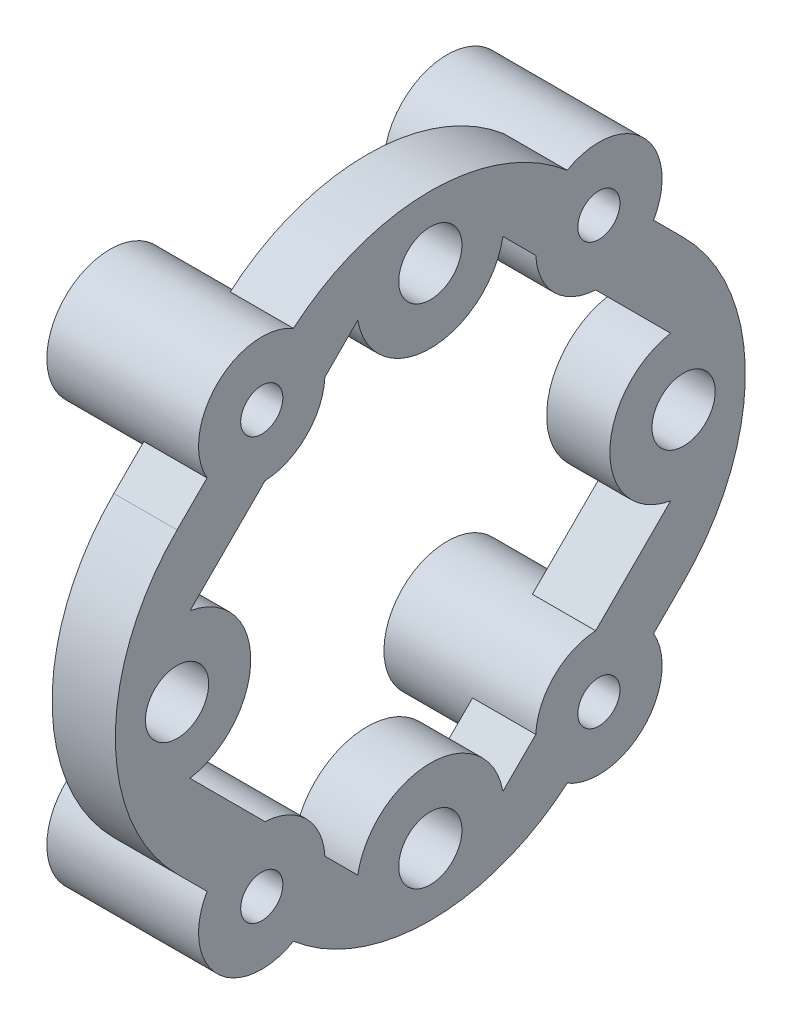
SolidWorks part; units mm, degrees
material "PET"
ref_plane "Front Plane" through (0, 0, 0) normal (0, 0, 1) x (1, 0, 0)
ref_plane "Top Plane" through (0, 0, 0) normal (0, 1, 0) x (1, 0, 0)
ref_plane "Right Plane" through (0, 0, 0) normal (1, 0, 0) x (0, 0, -1)
sketch "Sketch1" plane through (49.1629, 0, 0) normal (1, 0, 0) x (0, 0, -1)
  line L0 (-3.3619, -4.0805) -> (20.6798, -4.0805) construction
  line L1 (8.659, -4.0805) -> (8.659, 7.9403) construction
  circle A19 centre (0.659, 5.9195) radius 1
  circle A21 centre (0.659, 5.9195) radius 1
  circle A22 centre (0.659, 5.9195) radius 3
  circle A24 centre (0.659, -14.0805) radius 1
  circle A25 centre (0.659, -14.0805) radius 1
  circle A26 centre (0.659, -14.0805) radius 3
  circle A27 centre (16.659, -14.0805) radius 3
  circle A28 centre (16.659, -14.0805) radius 1
  circle A29 centre (16.659, 5.9195) radius 3
  circle A30 centre (16.659, 5.9195) radius 1
  dimension "D1" = 0
  dimension "D2" = 0
  dimension "D3" = 2
  dimension "D4" = 2
extrude "Boss-Extrude1" add sketch "Sketch1" along normal up to surface (7.2 mm away)
sketch "Sketch2" plane through (56.3629, 0, 0) normal (1, 0, 0) x (0, 0, -1)
  line L0 (-3.3619, -4.0805) -> (-0.887, -1.6056)
  line L1 (8.659, 7.9403) -> (11.1338, 5.4654)
  line L2 (-3.3619, -4.0805) -> (-0.887, -6.5554)
  line L3 (8.659, -16.1013) -> (11.1338, -13.6264)
  line L4 (-6.1903, -4.0805) -> (8.659, 10.7687)
  line L5 (8.659, 10.7687) -> (23.5082, -4.0805)
  line L6 (8.659, -18.9297) -> (23.5082, -4.0805)
  line L7 (-6.1903, -4.0805) -> (8.659, -18.9297)
  line L8 (6.1841, 5.4654) -> (8.659, 7.9403)
  line L9 (-3.3619, -4.0805) -> (8.659, 7.9403) construction
  line L10 (18.2049, -1.6056) -> (20.6798, -4.0805)
  line L11 (8.659, 7.9403) -> (20.6798, -4.0805) construction
  line L12 (18.2049, -6.5554) -> (20.6798, -4.0805)
  line L13 (8.659, -16.1013) -> (20.6798, -4.0805) construction
  line L14 (6.1841, -13.6264) -> (8.659, -16.1013)
  line L15 (-3.3619, -4.0805) -> (8.659, -16.1013) construction
  line L16 (-10.4329, -4.0805) -> (8.659, 15.0114)
  line L17 (8.659, 15.0114) -> (27.7508, -4.0805)
  line L18 (8.659, -23.1724) -> (27.7508, -4.0805)
  line L19 (-10.4329, -4.0805) -> (8.659, -23.1724)
  circle A2 centre (8.659, 7.9403) radius 1.5
  circle A3 centre (8.659, 7.9403) radius 1.5
  circle A5 centre (20.6798, -4.0805) radius 1.5
  circle A6 centre (20.6798, -4.0805) radius 1.5
  circle A10 centre (-3.3619, -4.0805) radius 1.5
  circle A11 centre (-3.3619, -4.0805) radius 1.5
  circle A12 centre (8.659, 7.9403) radius 3.5
  circle A13 centre (8.659, -16.1013) radius 1.5
  circle A14 centre (8.659, -16.1013) radius 1.5
  circle A15 centre (20.6798, -4.0805) radius 3.5
  circle A16 centre (-3.3619, -4.0805) radius 3.5
  circle A17 centre (8.659, -16.1013) radius 3.5
  circle A24 centre (0.659, 5.9195) radius 1
  circle A25 centre (0.659, 5.9195) radius 1
  circle A27 centre (16.659, 5.9195) radius 1
  circle A28 centre (16.659, 5.9195) radius 1
  circle A30 centre (0.659, -14.0805) radius 1
  circle A31 centre (0.659, -14.0805) radius 1
  circle A33 centre (16.659, -14.0805) radius 1
  circle A34 centre (16.659, -14.0805) radius 1
  circle M8 centre (0.659, 5.9195) radius 3
  dimension "D1" = 0
  dimension "D2" = 0
  dimension "D3" = 0
  dimension "D4" = 0
  dimension "D5" = 2
  dimension "D6" = 2
  dimension "D7" = 2
  dimension "D8" = 2
  dimension "D9" = 2
  dimension "D10" = 3
  dimension "D11" = 0
  dimension "D12" = 0
  dimension "D13" = 0
  dimension "D14" = 0
extrude "Boss-Extrude2" add sketch "Sketch2" against normal blind 3 contours A17 L7 A16 L4 L16 L19 L18 L17 A12 L5 A15 L6 M8 | L4 A12 L8 A3 L1 L5 | L5 A12 L4 | L8 A12 L1 A3 | L6 A15 L5 | L5 A15 L10 A6 L12 L6 | L10 A15 L12 A6 | L7 A17 L6 | L6 A17 L3 A14 L14 L7 | L3 A17 L14 A14 | L2 A16 L0 A11 | L0 A16 L4 L7 L2 A11 | L4 A16 L7 region at (56.3629, -4.0805, 4.9488) region at (56.3629, -4.0805, 0.991) region at (56.3629, -4.0805, 7.4019) region at (56.3629, -2.3005, 4.5251) region at (56.3629, -14.5214, -5.6336) region at (56.3629, -17.2646, -6.8789) region at (56.3629, -13.7305, -8.659) region at (56.3629, 11.3457, -8.3565) region at (56.3629, 8.9846, -6.9978) region at (56.3629, 5.5695, -8.659) region at (56.3629, -7.1058, -19.0998) region at (56.3629, -5.8605, -21.843) region at (56.3629, -4.0805, -18.3089)
fillet "Fillet1" radius 10 4 edges at (54.8629, 15.0114, -8.659) (54.8629, -4.0805, -27.7508) (54.8629, -4.0805, 10.4329) (54.8629, -23.1724, -8.659)
